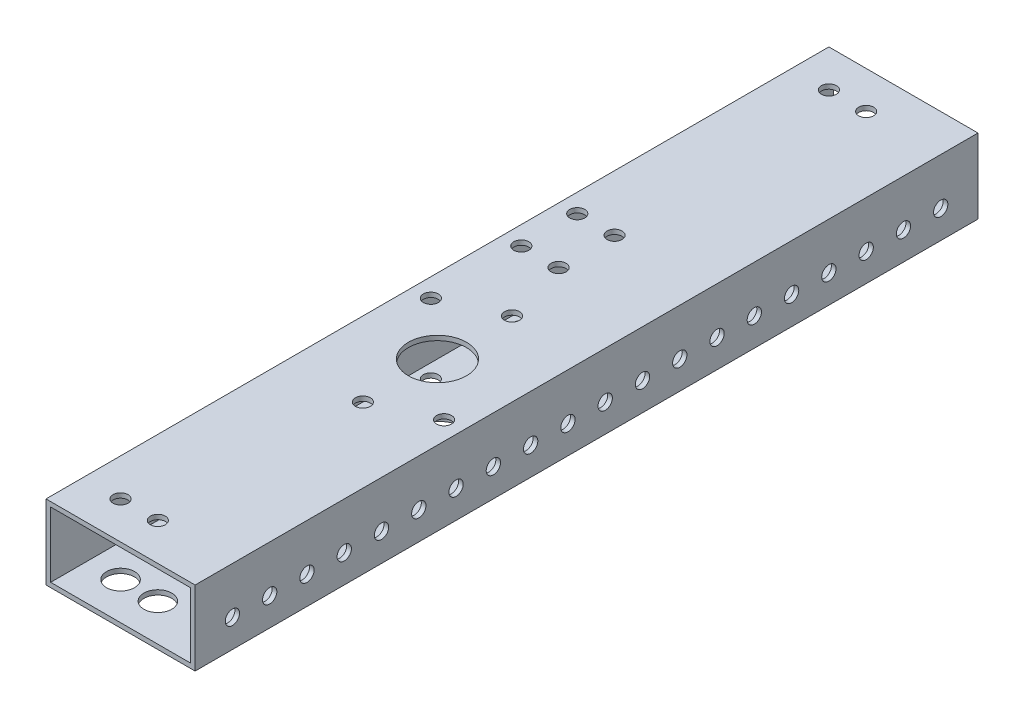
SolidWorks part; units mm, degrees
other "Markup1"
sketch "Sketch7" plane through (25.4, 12.7, -127) normal (0.9965, 0.0171, -0.0817) x (-0.082, 0.0128, -0.9966)
sketch "Sketch8" plane through (25.4, 12.7, -127) normal (0.9965, 0.0171, -0.0817) x (-0.082, 0.0128, -0.9966)
sketch "Sketch9" plane through (25.4, 12.7, -127) normal (0.9965, 0.0171, -0.0817) x (-0.082, 0.0128, -0.9966)
sketch "Sketch12" plane through (25.4, 12.7, -127) normal (0.9965, 0.0171, -0.0817) x (-0.082, 0.0128, -0.9966)
sketch "Sketch13" plane through (25.4, 12.7, -127) normal (0.9965, 0.0171, -0.0817) x (-0.082, 0.0128, -0.9966)
sketch "Sketch14" plane through (25.4, 12.7, -127) normal (0.9965, 0.0171, -0.0817) x (-0.082, 0.0128, -0.9966)
sketch "Sketch15" plane through (25.4, 12.7, -133.35) normal (0.9965, 0.0171, -0.0817) x (-0.082, 0.0128, -0.9966)
sketch "Sketch16" plane through (25.4, 12.7, -133.35) normal (0.9965, 0.0171, -0.0817) x (-0.082, 0.0128, -0.9966)
sketch "Sketch17" plane through (25.4, 12.7, -133.35) normal (0.9965, 0.0171, -0.0817) x (-0.082, 0.0128, -0.9966)
sketch "Sketch18" plane through (25.4, 12.7, -133.35) normal (0.9965, 0.0171, -0.0817) x (-0.082, 0.0128, -0.9966)
material "6061-T6 (SS)"
ref_plane "Front Plane" through (0, 0, 0) normal (0, 0, 1) x (1, 0, 0)
ref_plane "Top Plane" through (0, 0, 0) normal (0, 1, 0) x (1, 0, 0)
ref_plane "Right Plane" through (0, 0, 0) normal (1, 0, 0) x (0, 0, -1)
sketch "Sketch1" plane through (0, 0, 0) normal (0, 0, 1) x (1, 0, 0)
  line L0 (-23.8125, 11.1125) -> (23.8125, 11.1125)
  line L1 (-25.4, -12.7) -> (25.4, -12.7)
  line L2 (-25.4, -12.7) -> (-25.4, 12.7)
  line L3 (-25.4, 12.7) -> (25.4, 12.7)
  line L4 (25.4, -12.7) -> (25.4, 12.7)
  line L5 (-25.4, -12.7) -> (25.4, 12.7) construction
  line L6 (-25.4, 12.7) -> (25.4, -12.7) construction
  line L7 (23.8125, -11.1125) -> (23.8125, 11.1125)
  line L8 (-23.8125, -11.1125) -> (23.8125, -11.1125)
  line L9 (-23.8125, -11.1125) -> (-23.8125, 11.1125)
  point P0 (0, 0)
  dimension "D1" = 50.8
  dimension "D2" = 25.4
  dimension "D3" = 1.5875
extrude "Boss-Extrude1" add sketch "Sketch1" along normal mid plane 266.7
sketch "Sketch3" plane through (0, 12.7, 0) normal (0, 1, 0) x (1, 0, 0)
  line L0 (25.4, 133.35) -> (-25.4, 133.35) construction
  line L1 (25.4, -133.35) -> (-25.4, -133.35) construction
  line L3 (-25.4, -133.35) -> (-25.4, 133.35) construction
  line L4 (25.4, -133.35) -> (25.4, 133.35) construction
  circle A0 centre (-12.7, -120.65) radius 2.5527
  circle A1 centre (0, -120.65) radius 2.5527
  circle A2 centre (-12.7, 120.65) radius 2.5527
  circle A3 centre (0, 120.65) radius 2.5527
  dimension "D5" = 5.1054
  dimension "D1" = 12.7
  dimension "D2" = 12.7
  dimension "D3" = 12.7
  dimension "D4" = 12.7
  dimension "D6" = 12.7
  dimension "D7" = 12.7
  dimension "D8" = 12.7
  dimension "D9" = 25.4
  dimension "D10" = 12.7
  dimension "D11" = 25.4
extrude "Cut-Extrude1" cut sketch "Sketch3" against normal up to surface (1.5875 mm away) up to face at (0, 11.1125, 0)
sketch "Sketch5" plane through (0, -12.7, 0) normal (0, -1, 0) x (1, 0, 0)
  circle A0 centre (-12.7, -120.65) radius 2.5527 construction
  circle A1 centre (0, -120.65) radius 2.5527 construction
  circle A2 centre (0, 120.65) radius 2.5527 construction
  circle A3 centre (-12.7, 120.65) radius 2.5527 construction
  circle A4 centre (-12.7, -120.65) radius 2.5527
  circle A5 centre (0, -120.65) radius 2.5527
  circle A6 centre (0, 120.65) radius 2.5527
  circle A7 centre (-12.7, 120.65) radius 2.5527
  circle A8 centre (-12.7, 120.65) radius 4.7625
  circle A9 centre (0, 120.65) radius 4.7625
  circle A10 centre (0, -120.65) radius 4.7625
  circle A11 centre (-12.7, -120.65) radius 4.7625
  dimension "D1" = 9.525
extrude "Cut-Extrude2" cut sketch "Sketch5" against normal up to surface (1.5875 mm away) contours A10 A5 | A5 | A11 A4 | A4 | A6 | A9 A6 | A8 A7 | A7 region at (-12.7, -12.7, -120.65) region at (0, -12.7, -120.65) region at (0, -12.7, 120.65) region at (-12.7, -12.7, 120.65) region at (-17.3278, -12.7, 120.65) region at (-4.6278, -12.7, 120.65) region at (-4.6278, -12.7, -120.65) region at (-17.3278, -12.7, -120.65) up to face at (0, -11.1125, 0)
sketch "Sketch6" plane through (25.4, 0, 0) normal (1, 0, 0) x (0, 0, -1)
  line L0 (-133.35, -12.7) -> (-133.35, 12.7) construction
  line L1 (-133.35, -12.7) -> (133.35, -12.7) construction
  line L2 (0, 12.7) -> (0, -12.7) construction
  line L3 (-133.35, 12.7) -> (133.35, 12.7) construction
  circle A0 centre (-120.65, -3.175) radius 2.4384
  circle A19 centre (-107.95, -3.175) radius 2.4384
  circle A20 centre (-95.25, -3.175) radius 2.4384
  circle A21 centre (-82.55, -3.175) radius 2.4384
  circle A22 centre (-69.85, -3.175) radius 2.4384
  circle A23 centre (-57.15, -3.175) radius 2.4384
  circle A24 centre (-44.45, -3.175) radius 2.4384
  circle A25 centre (-31.75, -3.175) radius 2.4384
  circle A26 centre (-19.05, -3.175) radius 2.4384
  circle A27 centre (-6.35, -3.175) radius 2.4384
  circle A28 centre (6.35, -3.175) radius 2.4384
  circle A29 centre (19.05, -3.175) radius 2.4384
  circle A30 centre (31.75, -3.175) radius 2.4384
  circle A31 centre (44.45, -3.175) radius 2.4384
  circle A32 centre (57.15, -3.175) radius 2.4384
  circle A33 centre (69.85, -3.175) radius 2.4384
  circle A34 centre (82.55, -3.175) radius 2.4384
  circle A35 centre (95.25, -3.175) radius 2.4384
  circle A36 centre (107.95, -3.175) radius 2.4384
  circle A37 centre (120.65, -3.175) radius 2.4384
  dimension "D1" = 4.8768
  dimension "D5" = 12.7
  dimension "D2" = 12.7
  dimension "D3" = 9.525
  dimension "D4" = 20
extrude "Cut-Extrude3" cut sketch "Sketch6" against normal up to next contours A0 | A19 | A20 | A21 | A23 | A22 | A24 | A25 | A26 | A27 | A28 | A29 | A30 | A31 | A32 | A37 | A36 | A35 | A34 | A33 | A24 | A33 region at (25.4, -3.175, 120.65) region at (25.4, -3.175, 107.95) region at (25.4, -3.175, 95.25) region at (25.4, -3.175, 82.55) region at (25.4, -3.175, 69.85) region at (25.4, -3.175, 57.15) region at (25.4, -3.175, 44.45) region at (25.4, -3.175, 31.75) region at (25.4, -3.175, 19.05) region at (25.4, -3.175, 6.35) region at (25.4, -3.175, -6.35) region at (25.4, -3.175, -19.05) region at (25.4, -3.175, -31.75) region at (25.4, -3.175, -44.45) region at (25.4, -3.175, -57.15) region at (25.4, -3.175, -69.85) region at (25.4, -3.175, -82.55) region at (25.4, -3.175, -95.25) region at (25.4, -3.175, -107.95) region at (25.4, -3.175, -120.65)
sketch "Sketch11" plane through (0, 12.7, 0) normal (0, 1, 0) x (1, 0, 0)
  line L0 (-25.4, -133.35) -> (-25.4, 133.35) construction
  line L1 (-6.35, 41.275) -> (-6.35, 22.225) construction
  line L2 (0, 0) -> (0, -50.8) construction
  line L3 (25.4, 133.35) -> (-25.4, 133.35) construction
  line L5 (-19.05, 41.275) -> (-3.7973, 41.275) construction
  line L6 (-19.05, 41.275) -> (-19.05, 22.225) construction
  line L7 (-19.05, 22.225) -> (-3.7973, 22.225) construction
  line L9 (-19.05, 41.275) -> (-16.8611, 39.9616) construction
  line L10 (-19.05, 22.225) -> (-16.8611, 23.5384) construction
  line L13 (-15.875, -34.925) -> (-15.875, -15.875) construction
  line L14 (19.05, -42.2005) -> (-19.05, -8.5995) construction
  circle A0 centre (0, -25.4) radius 9.906
  circle A1 centre (0, 0) radius 2.5527
  circle A2 centre (0, -50.8) radius 2.5527
  circle A4 centre (-19.05, 22.225) radius 2.5527
  circle A5 centre (-19.05, 41.275) radius 2.5527
  circle A7 centre (-6.35, 22.225) radius 2.5527
  circle A8 centre (-6.35, 41.275) radius 2.5527
  circle A13 centre (-19.05, -8.5995) radius 2.5527
  circle A14 centre (19.05, -42.2005) radius 2.5527
  point P2 (0, -25.4)
  point P8 (-3.175, 31.75)
  point P24 (0, -25.4)
  dimension "D1" = 19.812
  dimension "D3" = 5.1054
  dimension "D4" = 25.4
  dimension "D5" = 19.05
  dimension "D6" = 5.1054
  dimension "D7" = 12.7
  dimension "D10" = 6.35
  dimension "D2" = 25.4
  dimension "D8" = 101.6
  dimension "D9" = 6.35
  dimension "D11" = 15.875
  dimension "D12" = 22.225
  dimension "1" = 25.4
extrude "Cut-Extrude4" cut sketch "Sketch11" against normal through all
